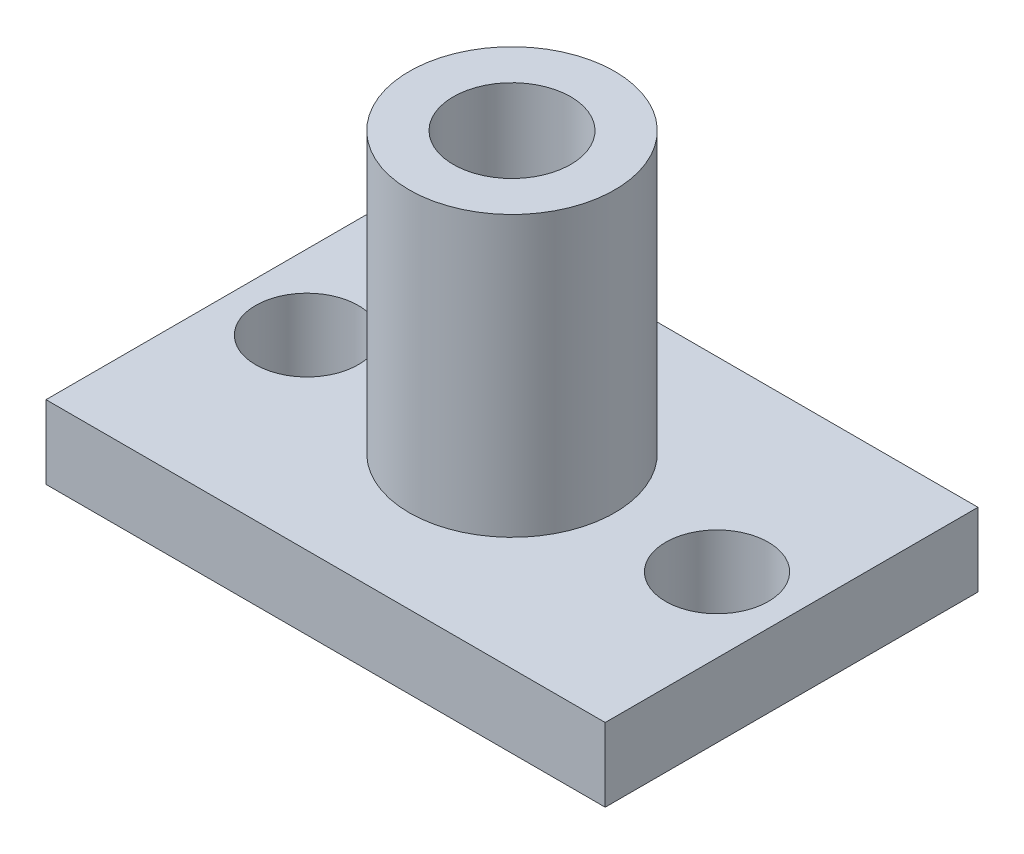
SolidWorks part; units mm, degrees
ref_plane "前视" through (0, 0, 0) normal (0, 0, 1) x (1, 0, 0)
ref_plane "上视" through (0, 0, 0) normal (0, 1, 0) x (1, 0, 0)
ref_plane "右视" through (0, 0, 0) normal (1, 0, 0) x (0, 0, -1)
sketch "Sketch1" plane through (0, 0, 0) normal (0, 1, 0) x (1, 0, 0)
  line L1 (-25.8417, 12.7) -> (12.2583, 12.7)
  line L2 (-25.8417, 12.7) -> (-25.8417, -12.7)
  line L3 (-25.8417, -12.7) -> (12.2583, -12.7)
  line L4 (12.2583, 12.7) -> (12.2583, -12.7)
  dimension "D1" = 25.4
  dimension "D2" = 38.1
extrude "Boss-Extrude1" add sketch "Sketch1" along normal blind 5
ref_point "Point1"
sketch "Sketch3" plane through (0, 5, 0) normal (0, 1, 0) x (1, 0, 0)
  circle A0 centre (-6.7917, 0) radius 7
  circle A1 centre (-6.7917, 0) radius 4
extrude "Boss-Extrude2" add sketch "Sketch3" along normal blind 19.05
ref_axis "Axis1" through (12.2583, 5, 0) along (-1, 0, 0)
sketch "Sketch4" plane through (0, 5, 0) normal (0, 1, 0) x (1, 0, 0)
  line L0 (12.2583, -12.7) -> (12.2583, 12.7) construction
  line L1 (-25.8417, 12.7) -> (-25.8417, -12.7) construction
  circle A0 centre (7.1783, 0) radius 3.5
  circle A1 centre (-20.7617, 0) radius 3.5
  point P0 (7.1783, 0)
  point P1 (12.2583, 0)
  point P4 (-20.7617, 0)
  dimension "D3" = 7
  dimension "D4" = 7
  dimension "D1" = 5.08
  dimension "D2" = 5.08
extrude "Cut-Extrude1" cut sketch "Sketch4" against normal through all
